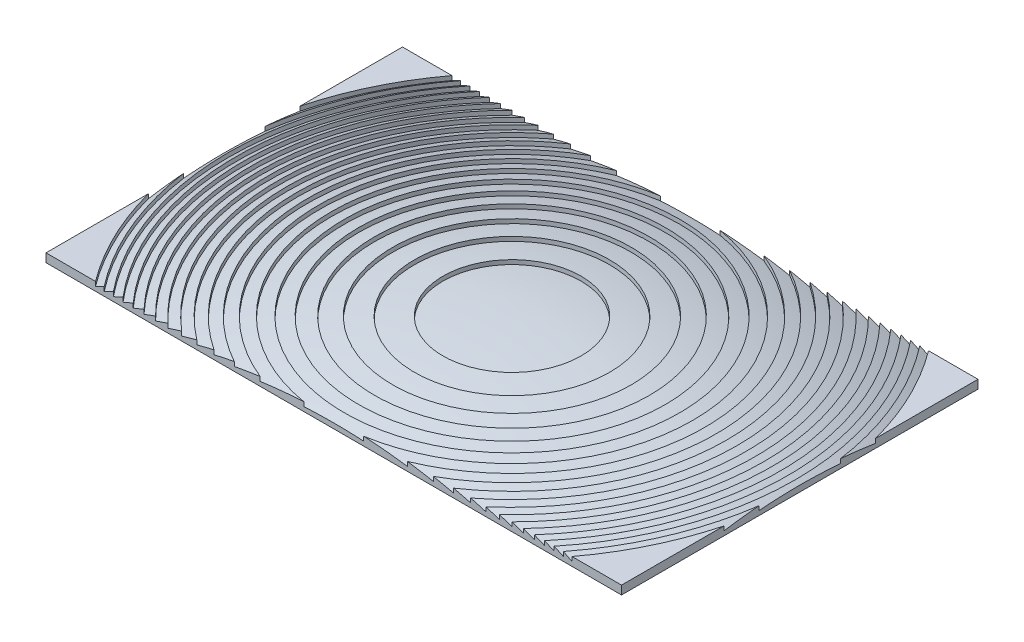
SolidWorks part; units mm, degrees
material "PMMA"
ref_plane "Front Plane" through (0, 0, 0) normal (0, 0, 1) x (1, 0, 0)
ref_plane "Top Plane" through (0, 0, 0) normal (0, 1, 0) x (1, 0, 0)
ref_plane "Right Plane" through (0, 0, 0) normal (1, 0, 0) x (0, 0, -1)
sketch "Sketch1" plane through (0, 0, 0) normal (0, 1, 0) x (1, 0, 0)
  line L1 (-67, -41.5) -> (67, -41.5)
  line L2 (-67, -41.5) -> (-67, 41.5)
  line L3 (-67, 41.5) -> (67, 41.5)
  line L4 (67, -41.5) -> (67, 41.5)
  point P4 (0, -41.5)
  point P6 (-67, 0)
  dimension "D1" = 134
  dimension "D2" = 83
extrude "Boss-Extrude1" add sketch "Sketch1" along normal mid plane 2
sketch "Sketch2" plane through (0, 0, 0) normal (0, 0, 1) x (1, 0, 0)
  line L0 (-67, 0) -> (67, 0) construction
  line L1 (-67, 1) -> (-67, -1) construction
  line L2 (67, 1) -> (67, -1) construction
  line L3 (0, 0) -> (0, 1) construction
  line L4 (-67, 1) -> (67, 1) construction
  line L5 (16.0935, 0) -> (16.0935, 1)
  line L6 (22.7156, 0) -> (22.7156, 1)
  line L7 (27.7669, 0) -> (27.7669, 1)
  line L8 (32, 0) -> (32, 1)
  line L9 (35.7071, 0) -> (35.7071, 1)
  line L10 (39.0384, 0) -> (39.0384, 1)
  line L11 (0, 1) -> (0, 2)
  line L12 (42.0833, 0) -> (42.0833, 1)
  line L13 (44.8999, 0) -> (44.8999, 1)
  line L14 (47.5289, 0) -> (47.5289, 1)
  line L15 (50, 0) -> (50, 1)
  line L16 (52.3355, 0) -> (52.3355, 1)
  line L17 (0, 2) -> (100, 2)
  line L18 (52.3355, 0) -> (52.3355, 1)
  line L19 (100, 2) -> (100, 0)
  line L20 (0, -129) -> (0, 0) construction
  line L21 (54.5527, 0) -> (54.5527, 1)
  line L22 (56.6657, 0) -> (56.6657, 1)
  line L23 (58.6856, 0) -> (58.6856, 1)
  line L24 (60.6218, 0) -> (60.6218, 1)
  line L25 (62.482, 0) -> (62.482, 1)
  line L26 (64.2729, 0) -> (64.2729, 1)
  line L27 (66, 0) -> (66, 1)
  line L28 (67.6683, 0) -> (67.6683, 1)
  line L29 (69.282, 0) -> (100, 0)
  line L30 (69.282, 0) -> (69.282, 2)
  line L31 (67, 0) -> (100, 0) construction
  line L32 (67, 1) -> (100, 1) construction
  arc A0 (0, 1) -> (16.0935, 0) centre (0, -129) cw
  arc A1 (16.0935, 1) -> (22.7156, 0) centre (0, -128) cw
  arc A2 (22.7156, 1) -> (27.7669, 0) centre (0, -127) cw
  arc A3 (27.7669, 1) -> (32, 0) centre (0, -126) cw
  arc A4 (32, 1) -> (35.7071, 0) centre (0, -125) cw
  arc A5 (35.7071, 1) -> (39.0384, 0) centre (0, -124) cw
  arc A6 (39.0384, 1) -> (42.0833, 0) centre (0, -123) cw
  arc A7 (42.0833, 1) -> (44.8999, 0) centre (0, -122) cw
  arc A8 (44.8999, 1) -> (47.5289, 0) centre (0, -121) cw
  arc A9 (47.5289, 1) -> (50, 0) centre (0, -120) cw
  arc A10 (50, 1) -> (52.3355, 0) centre (0, -119) cw
  arc A11 (52.3355, 1) -> (54.5527, 0) centre (0, -118) cw
  arc A12 (54.5527, 1) -> (56.6657, 0) centre (0, -117) cw
  arc A13 (56.6657, 1) -> (58.6856, 0) centre (0, -116) cw
  arc A14 (58.6856, 1) -> (60.6218, 0) centre (0, -115) cw
  arc A15 (60.6218, 1) -> (62.482, 0) centre (0, -114) cw
  arc A16 (62.482, 1) -> (64.2729, 0) centre (0, -113) cw
  arc A17 (64.2729, 1) -> (66, 0) centre (0, -112) cw
  arc A18 (66, 1) -> (67.6683, 0) centre (0, -111) cw
  arc A19 (67.6683, 1) -> (69.282, 0) centre (0, -110) cw
  dimension "D1" = 130
  dimension "D2" = 100
revolve "Cut-Revolve2" cut sketch "Sketch2" angle 360 about L3 region at (35.7318, 1.2426, 0)
